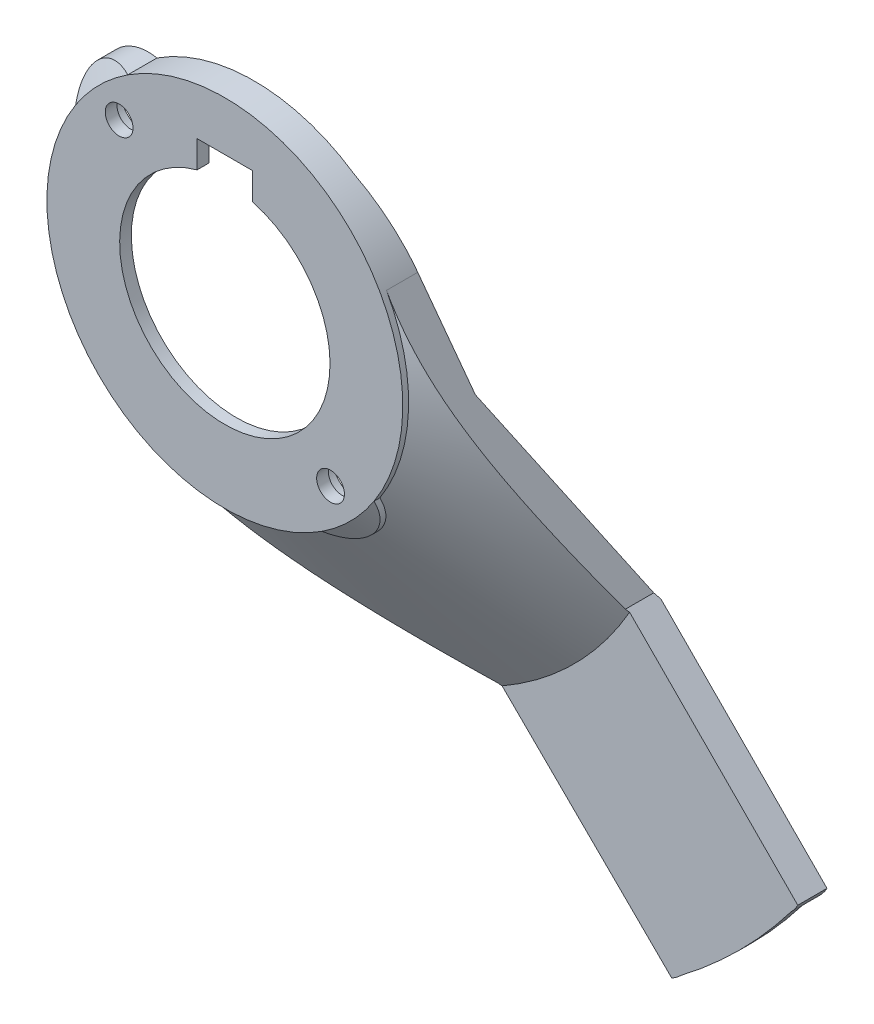
SolidWorks part; units mm, degrees
ref_plane "Front Plane" through (0, 0, 0) normal (0, 0, 1) x (1, 0, 0)
ref_plane "Top Plane" through (0, 0, 0) normal (0, 1, 0) x (1, 0, 0)
ref_plane "Right Plane" through (0, 0, 0) normal (1, 0, 0) x (0, 0, -1)
sketch "Sketch1" plane through (0, 0, 0) normal (1, 0, 0) x (0, 0, -1)
  line L0 (0, 0) -> (0, 30.95)
  line L1 (0, 30.95) -> (17.13, 59.4478)
  line L2 (17.13, 59.4478) -> (17.13, 77.9678)
  line L3 (17.13, 77.9678) -> (0, 77.9678)
  line L4 (0, 30.95) -> (0, 77.9678) construction
  dimension "D1" = 30.95
  dimension "D2" = 18.52
  dimension "D3" = 33.25
  dimension "D4" = 17.13
sketch "Sketch14" plane through (0, 0, 0) normal (1, 0, 0) x (0, 0, -1)
  line L0 (0, 0) -> (18.2751, 0)
sketch "Sketch2" plane through (0, 0, 0) normal (1, 0, 0) x (0, 0, -1)
  line L0 (0, 0) -> (0, 30.45)
  line L1 (0, 0) -> (0, 30.95) construction
  line L3 (17.13, 59.4478) -> (17.13, 77.9678) construction
  line L4 (0, 30.45) -> (1, 30.45)
  line L5 (18.13, 58.9432) -> (18.13, 98.9432)
  line L9 (1, 30.45) -> (18.13, 58.9432)
  line L10 (2, 0) -> (2, 23.45)
  line L12 (5, 33.2218) -> (20.13, 58.3883)
  line L13 (20.13, 58.3883) -> (20.13, 98.9432)
  line L14 (0, 0) -> (2, 0)
  line L15 (18.13, 98.9432) -> (20.13, 98.9432)
  line L17 (2, 0) -> (2, 28.45) construction
  line L18 (2, 28.45) -> (2.1312, 28.45) construction
  line L23 (5, 33.2218) -> (5, 27.7344)
  line L24 (2.1312, 28.45) -> (20.13, 58.3883) construction
  line L26 (5, 27.7344) -> (2, 23.45)
  point P17 (3.8994, 31.5584)
  dimension "D1" = 0.5
  dimension "D2" = 1
  dimension "D3" = 40
  dimension "D4" = 1
  dimension "D6" = 3
  dimension "D7" = 145
  dimension "D8" = 7
  dimension "D5" = 2
revolve "Revolve2" add sketch "Sketch2" angle 360 about L14
sketch "Sketch5" plane through (0, 0, 0) normal (0, 0, 1) x (1, 0, 0)
  line L0 (0, 0) -> (35355.3391, -35355.3391) construction
  line L1 (0, 0) -> (43301.2702, -25000) construction
  line L2 (0, 0) -> (25000, -43301.2702) construction
  line L3 (0, 0) -> (0, 30.95) construction
  line L6 (29.4716, -51.0464) -> (58.3394, -79.9142)
  line L7 (51.0464, -29.4716) -> (79.9142, -58.3394)
  line L8 (0, 0) -> (35355.3391, 35355.3391) construction
  line L9 (51.0464, -29.4716) -> (26.659, 14.7139)
  line L10 (29.4716, -51.0464) -> (-14.7139, -26.659)
  circle A0 centre (0, 0) radius 58.9432 construction
  circle A1 centre (0, 0) radius 30.45 construction
  circle A2 centre (0, 0) radius 30.45 construction
  arc A4 (26.659, 14.7139) -> (-14.7139, -26.659) centre (0, 0) ccw
  circle A5 centre (0, 0) radius 98.9432 construction
  arc A6 (79.9142, -58.3394) -> (58.3394, -79.9142) centre (0, 0) ccw
  point P22 (-14.7139, -26.659)
  point P27 (-15.8467, -26.0016)
  dimension "D1" = 135
  dimension "D2" = 15
  dimension "D3" = 15
extrude "Cut-Extrude1" cut sketch "Sketch5" against normal blind 50
sketch "Sketch7" plane through (0, 0, -2) normal (0, 0, -1) x (-1, 0, 0)
  line L0 (0, 0) -> (18.0878, 18.0878) construction
  circle A11 centre (18.0878, 18.0878) radius 7.58
  circle A12 centre (-18.0878, -18.0878) radius 7.58
  point P11 (0, 0)
  point P13 (0, 0)
  point P23 (0, 0)
  dimension "D1" = 25.58
  dimension "D2" = 2
extrude "Boss-Extrude1" add sketch "Sketch7" along normal up to surface and the other way up to surface up to face at (27.7344, 0, -5) other way up to face at (30.45, 0, 0)
sketch "Sketch6" plane through (0, 0, 0) normal (0, 0, 1) x (1, 0, 0)
  line L0 (-4.75, 22) -> (4.75, 22)
  line L1 (0, 18) -> (4.75, 18) construction
  line L2 (0, -18) -> (0, 22) construction
  line L3 (4.75, 22) -> (4.75, 17.362)
  line L4 (-4.75, 22) -> (-4.75, 17.362)
  arc A2 (4.75, 17.362) -> (-4.75, 17.362) centre (0, 0) cw
  dimension "D1" = 4.75
  dimension "D2" = 40
extrude "Cut-Extrude2" cut sketch "Sketch6" against normal through all contours A2 L3 L0 L4 region at (0, 0.7522, 0)
sketch "Sketch13" plane through (0, 0, 0) normal (1, 0, 0) x (0, 0, -1)
  line L0 (0, 30.45) -> (9.1585, 45.6863)
  line L1 (0, 30.95) -> (17.13, 59.4478) construction
  line L2 (9.1585, 45.6863) -> (-1.2585, 45.6863)
  line L3 (-1.2585, 45.6863) -> (-1.2585, 30.45)
  line L4 (-1.2585, 30.45) -> (0, 30.45)
revolve "Cut-Revolve1" cut sketch "Sketch13" angle 360 about L0
chamfer "Chamfer1" distance 1 angle 45 2 edges at (12.7279, -12.7279, -5) (-12.7279, 12.7279, -5)
sketch "Sketch16" plane through (0, 0, -5) normal (0, 0, -1) x (-1, 0, 0)
  circle A0 centre (18.0878, 18.0878) radius 2.375
  circle A1 centre (-18.0878, -18.0878) radius 2.375
  point P7 (0, 0)
  dimension "D1" = 2
extrude "Cut-Extrude6" cut sketch "Sketch16" against normal through all
sketch "Sketch17" plane through (0, 0, -5) normal (0, 0, -1) x (-1, 0, 0)
  circle A0 centre (18.0878, 18.0878) radius 5
  circle A1 centre (-18.0878, -18.0878) radius 5
  point P7 (0, 0)
  dimension "D1" = 2
extrude "Cut-Extrude7" cut sketch "Sketch17" against normal up to surface (3 mm away) up to face at (3.8406, 12.9883, -2)
sketch "Sketch19" plane through (0, 0, -5) normal (0, 0, -1) x (-1, 0, 0)
  line L10 (-59.9596, -78.7059) -> (-30.8356, -49.5819)
  line L11 (-58.3394, -79.9142) -> (-29.4716, -51.0464) construction
  line L12 (-30.8356, -49.5819) -> (-1.1574, -33.2016)
  line L13 (-28.9032, -50.7326) -> (3.0831, -33.0784) construction
  line L14 (-1.1574, -33.2016) -> (25.1801, -17.1221)
  line L16 (14.7139, -26.659) -> (-28.9032, -50.7326)
  line L17 (-28.9032, -50.7326) -> (-58.3394, -79.9142)
  line L18 (0, 0) -> (-35355.3391, -35355.3391) construction
  line L20 (-33.2016, -1.1574) -> (-17.1221, 25.1801)
  line L21 (-26.659, 14.7139) -> (-50.7326, -28.9032)
  line L22 (-49.5819, -30.8356) -> (-33.2016, -1.1574)
  line L23 (-50.7326, -28.9032) -> (-79.9142, -58.3394)
  line L24 (-78.7059, -59.9596) -> (-49.5819, -30.8356)
  arc A4 (-79.9142, -58.3394) -> (-58.3394, -79.9142) centre (0, 0) ccw construction
  arc A5 (-50.7326, -28.9032) -> (-28.9032, -50.7326) centre (0, 0) ccw construction
  arc A6 (-33.0784, 3.0831) -> (3.0831, -33.0784) centre (0, 0) ccw construction
  arc A7 (14.7139, -26.659) -> (25.522, 16.6082) centre (0, 0) ccw construction
  arc A8 (25.1801, -17.1221) -> (14.7139, -26.659) centre (0, 0) cw
  arc A9 (-59.9596, -78.7059) -> (-58.3394, -79.9142) centre (-55.0003, -73.7466) ccw
  arc A10 (-17.1221, 25.1801) -> (-26.659, 14.7139) centre (0, 0) ccw
  arc A11 (-78.7059, -59.9596) -> (-79.9142, -58.3394) centre (-73.7466, -55.0003) cw
  dimension "D1" = 2
extrude "Boss-Extrude2" add sketch "Sketch19" along normal offset from surface (18.13 mm away) 3 up to face at (50.1188, -50.1188, -20.13) offset beyond the face yes
sketch "Sketch24" plane through (0, 0, 0) normal (1, 0, 0) x (0, 0, -1)
  line L1 (2.6292, 33.16) -> (2.6292, 108.9432)
  line L3 (2.6292, 108.9432) -> (18.13, 108.9432)
  line L5 (18.13, 58.9432) -> (18.13, 108.9432)
  line L9 (2.6292, 33.16) -> (18.13, 58.9432)
  line L27 (2.6292, 33.16) -> (2.6292, -26.7764) construction
  line L28 (18.13, 58.9432) -> (2.6292, 33.16)
  spline S0 degree 3 poles (1, -25.522) (1.2495, -25.6379) (1.4737, -25.6859) (1.7737, -25.6497) (1.8682, -25.6191) (2.0416, -25.52) (2.1201, -25.452) (2.2613, -25.2789) (2.324, -25.1739) (2.4332, -24.925) (2.48, -24.7798) (2.5912, -24.2962) (2.6289, -23.9089) (2.6294, -23.227) (2.62, -22.9856) (2.5831, -22.483) (2.5554, -22.2208) (2.4819, -21.6744) (2.4355, -21.3882) (2.3264, -20.8091) (2.2637, -20.5151) (2.0515, -19.6205) (1.8758, -19.0012) (1.576, -18.0939) (1.4698, -17.7935) (1.2444, -17.1968) (1.1248, -16.8996) (1, -16.6082) knots 0 0 0 0 0.125 0.125 0.1875 0.1875 0.25 0.25 0.3125 0.3125 0.375 0.375 0.5 0.5 0.5625 0.5625 0.625 0.625 0.6875 0.6875 0.75 0.75 0.875 0.875 0.9375 0.9375 1 1 1 1 construction
  dimension "D3" = 50
revolve "Cut-Revolve2" cut sketch "Sketch24" angle 360 about L0 region at (0, 77.057, -9.8501)
sketch "Sketch27" plane through (23.6718, 14.452, 0) normal (-0.8535, -0.5211, 0) x (0, 0, 1)
  line L0 (-23.13, 12.5693) -> (-8, 12.5693)
  line L1 (-23.13, 12.5693) -> (-5, 12.5693) construction
  line L3 (-23.13, -18.2886) -> (-5, -18.2886) construction
  line L4 (-8, -18.2886) -> (-23.13, -52.1546)
  line L5 (-23.13, -52.1546) -> (-23.13, 12.5693)
  line L6 (-8, -18.2886) -> (-5, 12.5693)
  line L7 (-5, 12.5693) -> (-8, 12.5693)
  dimension "D1" = 3
extrude "Cut-Extrude8" cut sketch "Sketch27" against normal blind 3 and the other way blind 3
sketch "Sketch28" plane through (-14.452, -23.6718, 0) normal (0.5211, 0.8535, 0) x (0.8535, -0.5211, 0)
  line L0 (18.2886, 5) -> (18.2886, 8) construction
  line L1 (18.2886, 23.13) -> (18.2886, 5) construction
  line L6 (18.2886, 8) -> (-12.5693, 5)
  line L7 (-12.5693, 5) -> (-12.5693, 23.13)
  line L8 (-12.5693, 23.13) -> (52.1546, 23.13)
  line L9 (52.1546, 23.13) -> (18.2886, 8)
  dimension "D1" = 3
extrude "Cut-Extrude9" cut sketch "Sketch28" against normal blind 3 and the other way blind 3
